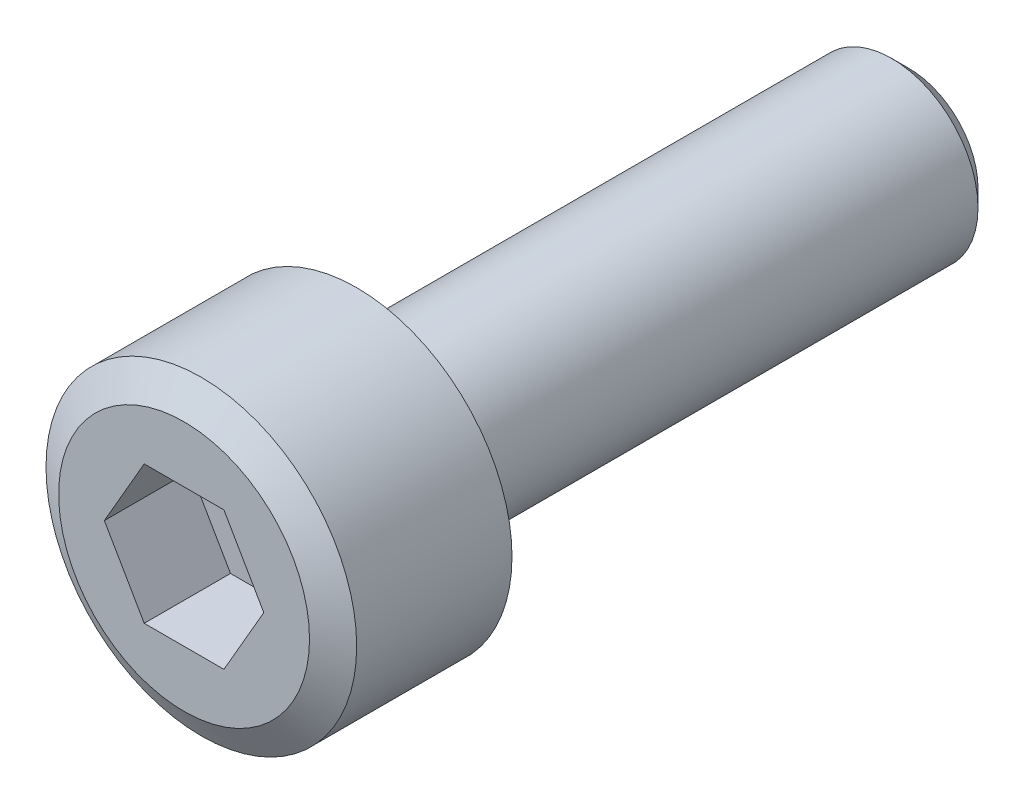
SolidWorks part; units mm, degrees
material "ALLOY STEEL, ASTM A 574M"
ref_plane "Front" through (0, 0, 0) normal (0, 0, 1) x (1, 0, 0)
ref_plane "Top" through (0, 0, 0) normal (0, 1, 0) x (1, 0, 0)
ref_plane "Side" through (0, 0, 0) normal (1, 0, 0) x (0, 0, -1)
ref_axis "Axis1" through (0, 0, 50) along (0, 0, -1)
sketch "Body_Sketch" plane through (0, 0, 0) normal (1, 0, 0) x (0, 0, -1)
  line L0 (0, 0) -> (28.4109, 0) construction
  line L1 (8, 0) -> (8, 1)
  line L2 (7.75, 1.25) -> (0.1, 1.25)
  line L3 (0, 1.35) -> (0, 2.25)
  line L4 (0, 2.25) -> (-2.25, 2.25)
  line L5 (-2.5, 1.817) -> (-2.5, 0)
  line L6 (-2.5, 0) -> (8, 0)
  line L7 (-2.25, 2.25) -> (-2.5, 1.817)
  line L8 (8, 1) -> (7.75, 1.25)
  arc A0 (0.1, 1.25) -> (0, 1.35) centre (0.1, 1.35) cw
  point P4 (8, 1.25)
  point P8 (-2.5, 2.25)
  point P13 (0, 1.25)
  dimension "Under_Fillet" = 0.1
  dimension "Head_Height" = 2.5
  dimension "Body_Length" = 8
  dimension "Head_Dia" = 4.5
  dimension "Body_Dia" = 2.5
  dimension "Head_Chamfer" = 0.25
  dimension "D6" = 60
  dimension "Point_Chamfer" = 0.25
  dimension "D9" = 45
revolve "Body_Revolve" add sketch "Body_Sketch" angle 360 about L0
sketch "Key_Sketch" plane through (0, 0, 2.5) normal (0, 0, 1) x (1, 0, 0)
  line L0 (0, 0) -> (1.1547, 0) construction
  line L1 (1.1547, 0) -> (0.5774, 1)
  line L2 (0.5774, 1) -> (-0.5774, 1)
  line L3 (-0.5774, 1) -> (-1.1547, 0)
  line L4 (-1.1547, 0) -> (-0.5774, -1)
  line L5 (-0.5774, -1) -> (0.5774, -1)
  line L6 (0.5774, -1) -> (1.1547, 0)
  circle A0 centre (0, 0) radius 1 construction
  dimension "Hex_Size" = 2
extrude "Hex_Cut" cut sketch "Key_Sketch" against normal blind 1.25
other "PropertyManager"
